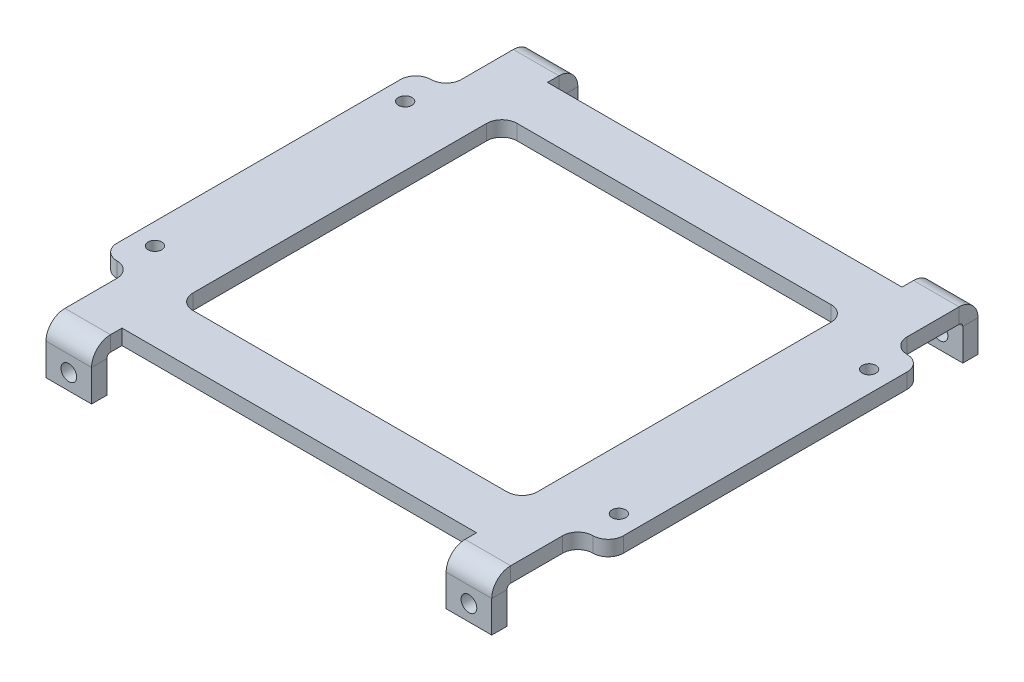
SolidWorks part; units mm, degrees
note: The reader was unsure of these and kept them because the rebuilt part matched: thickness of "Base-Flange1", "Edge-Flange1", "Sheet-Metal1", "Sheet-Metal2", "Sheet-Metal3", "Sheet-Metal4"; flange length of "Edge-Flange1".
material "6061-T6 (SS)"
ref_plane "Front Plane" through (0, 0, 0) normal (0, 0, 1) x (1, 0, 0)
ref_plane "Top Plane" through (0, 0, 0) normal (0, 1, 0) x (1, 0, 0)
ref_plane "Right Plane" through (0, 0, 0) normal (1, 0, 0) x (0, 0, -1)
sketch "Sketch1" plane through (0, 0, 0) normal (0, 1, 0) x (1, 0, 0)
  line L0 (50, -50) -> (-50, -50) construction
  line L1 (50, -50) -> (50, 50) construction
  line L2 (50, 50) -> (-50, 50) construction
  line L3 (-50, -50) -> (-50, 50) construction
  line L4 (50, -50) -> (-50, 50) construction
  line L5 (50, 50) -> (-50, -50) construction
  line L6 (-50, 50) -> (-44, 50) construction
  line L7 (-50, 50) -> (-50, 44) construction
  line L8 (-50, 44) -> (-44, 44) construction
  line L9 (-44, 50) -> (-44, 44) construction
  line L10 (-50, -50) -> (-44, -50) construction
  line L11 (-50, -50) -> (-50, -44) construction
  line L12 (-50, -44) -> (-44, -44) construction
  line L13 (-44, -50) -> (-44, -44) construction
  line L14 (50, -50) -> (44, -50) construction
  line L15 (50, -50) -> (50, -44) construction
  line L16 (50, -44) -> (44, -44) construction
  line L17 (44, -50) -> (44, -44) construction
  line L18 (50, 50) -> (44, 50) construction
  line L19 (50, 50) -> (50, 44) construction
  line L20 (50, 44) -> (44, 44) construction
  line L21 (44, 50) -> (44, 44) construction
  line L22 (-32.625, 45.061) -> (33.923, 45.061) construction
  line L23 (-32.625, 45.061) -> (-32.625, 35.082) construction
  line L24 (-32.625, 35.082) -> (33.923, 35.082) construction
  line L25 (33.923, 45.061) -> (33.923, 35.082) construction
  line L26 (-50, 50) -> (-35, 50)
  line L27 (-50, 50) -> (-50, 48)
  line L28 (-50, 48) -> (-35, 48)
  line L29 (-35, 50) -> (-35, 48)
  line L30 (-50, 50) -> (-48, 50)
  line L31 (-50, 50) -> (-50, 35)
  line L32 (-50, 35) -> (-48, 35)
  line L33 (-48, 50) -> (-48, 35)
  line L34 (50, 50) -> (35, 50)
  line L35 (50, 50) -> (50, 48)
  line L36 (50, 48) -> (35, 48)
  line L37 (35, 50) -> (35, 48)
  line L38 (50, 50) -> (48, 50)
  line L39 (50, 50) -> (50, 35)
  line L40 (50, 35) -> (48, 35)
  line L41 (48, 50) -> (48, 35)
  line L42 (50, -50) -> (48, -50)
  line L43 (50, -50) -> (50, -35)
  line L44 (50, -35) -> (48, -35)
  line L45 (48, -50) -> (48, -35)
  line L46 (50, -50) -> (35, -50)
  line L47 (50, -50) -> (50, -48)
  line L48 (50, -48) -> (35, -48)
  line L49 (35, -50) -> (35, -48)
  line L50 (-50, -50) -> (-35, -50)
  line L51 (-50, -50) -> (-50, -48)
  line L52 (-50, -48) -> (-35, -48)
  line L53 (-35, -50) -> (-35, -48)
  line L54 (-50, -50) -> (-48, -50)
  line L55 (-50, -50) -> (-50, -35)
  line L56 (-50, -35) -> (-48, -35)
  line L57 (-48, -50) -> (-48, -35)
  circle A0 centre (-36.2, 42.85) radius 1.6
  circle A1 centre (37.5, 42.85) radius 1.6
  circle A2 centre (40, -42.85) radius 1.6
  circle A3 centre (-40, -42.85) radius 1.6
  point P0 (0, 0)
  point P5 (0, 0)
  point P6 (0, 0)
  dimension "D6" = 3.2
  dimension "D1" = 100
  dimension "D2" = 6
  dimension "D3" = 6
  dimension "D4" = 6
  dimension "D5" = 6
  dimension "D7" = 7.15
  dimension "D8" = 13.8
  dimension "D9" = 10
  dimension "D10" = 7.15
  dimension "D11" = 10
  dimension "D12" = 7.15
  dimension "D13" = 17.375
  dimension "D14" = 4.939
  dimension "D15" = 14.918
  dimension "D16" = 16.077
  dimension "D17" = 73.7
  dimension "D18" = 15
  dimension "D19" = 2
  dimension "D20" = 15
  dimension "D21" = 2
  dimension "D22" = 2
  dimension "D23" = 15
  dimension "D24" = 15
  dimension "D25" = 2
  dimension "D26" = 15
  dimension "D27" = 2
  dimension "D28" = 2
  dimension "D29" = 15
  dimension "D30" = 15
  dimension "D31" = 15
  dimension "D32" = 2
  dimension "D33" = 2
  dimension "D34" = 100
sketch "Sketch2" plane through (0, 0, 0) normal (0, 1, 0) x (1, 0, 0)
  line L5 (-50, -50) -> (-50, 50) construction
  line L6 (50, -31) -> (-50, -31)
  line L13 (50, -31) -> (50, 31)
  line L14 (50, 31) -> (-50, 31)
  line L16 (-50, -31) -> (-50, 31)
  line L17 (50, -31) -> (-50, 31) construction
  line L18 (50, 31) -> (-50, -31) construction
  line L19 (-50, 48) -> (-35, 48) construction
  line L20 (44, -48) -> (-44, -48)
  line L21 (44, -48) -> (44, 48)
  line L22 (44, 48) -> (-44, 48)
  line L23 (-44, -48) -> (-44, 48)
  line L24 (44, -48) -> (-44, 48) construction
  line L25 (44, 48) -> (-44, -48) construction
  line L26 (-44, 50) -> (-44, 44) construction
  point P0 (0, 0)
  point P8 (0, 0)
  dimension "D1" = 62
sketch "Sketch3" plane through (0, 0, 0) normal (0, 1, 0) x (1, 0, 0)
  line L0 (50, 31) -> (-50, 31) construction
  line L1 (-50, -31) -> (-50, 31) construction
  line L2 (50, -31) -> (-50, -31) construction
  line L3 (50, -31) -> (50, 31) construction
  line L4 (44, 48) -> (-44, 48) construction
  line L5 (-44, -48) -> (-44, 48) construction
  line L6 (44, -48) -> (-44, -48) construction
  line L7 (44, -48) -> (44, 48) construction
  line L8 (50, 31) -> (44, 31)
  line L9 (-50, -31) -> (-50, 31)
  line L10 (50, -31) -> (44, -31)
  line L11 (50, -31) -> (50, 31)
  line L12 (44, 48) -> (35, 48)
  line L13 (-44, -48) -> (-44, -31)
  line L14 (44, -48) -> (35, -48)
  line L15 (44, -48) -> (44, -31)
  line L16 (-44, 31) -> (-50, 31)
  line L17 (-44, 31) -> (-44, 48)
  line L18 (-44, -31) -> (-50, -31)
  line L19 (44, 31) -> (44, 48)
  line L20 (35, 50) -> (35, 48) construction
  line L22 (-35, 48) -> (-35, 42)
  line L23 (-35, 42) -> (35, 42)
  line L24 (35, 48) -> (35, 42)
  line L26 (-35, -48) -> (-35, -42)
  line L27 (-35, -42) -> (35, -42)
  line L28 (35, -48) -> (35, -42)
  line L29 (-35, 48) -> (-44, 48)
  line L30 (34, -32) -> (-34, -32)
  line L31 (34, -32) -> (34, 32)
  line L32 (34, 32) -> (-34, 32)
  line L33 (-34, -32) -> (-34, 32)
  line L34 (34, -32) -> (-34, 32) construction
  line L35 (34, 32) -> (-34, -32) construction
  line L36 (-35, -48) -> (-44, -48)
  point P24 (0, 0)
  dimension "D1" = 6
  dimension "D2" = 10
  dimension "D3" = 10
sketch "Sketch21" plane through (0, 0, 0) normal (0, 1, 0) x (1, 0, 0)
  line L1 (45.8, -24.7) -> (-45.8, -24.7)
  line L2 (45.8, -24.7) -> (45.8, 24.7)
  line L3 (45.8, 24.7) -> (-45.8, 24.7)
  line L4 (-45.8, -24.7) -> (-45.8, 24.7)
  line L5 (45.8, -24.7) -> (-45.8, 24.7) construction
  line L6 (45.8, 24.7) -> (-45.8, -24.7) construction
  point P0 (0, 0)
  dimension "D1" = 91.6
  dimension "D2" = 49.4
base flange "Base-Flange1" sketch "Sketch3" thickness 3 reverse thickness direction no parameters "D1"=0.7366
edge flange "Edge-Flange1" sketch "Sketch16" flange profiles "Sketch16", "Sketch17", "Sketch18", "Sketch19" flange angle 90 flange length 10 flange position material inside bend radius 0.7366 thickness 3 relief rectangular parameters "D6"=10, "D8"=1
sketch "Sketch16" plane through (0, -3, 48) normal (0, 0, -1) x (1, 0, 0)
  line L2 (-44, 0) -> (-44, 7)
  line L3 (-44, 7) -> (-35, 7)
  line L4 (-35, 7) -> (-35, 0)
  line L5 (-35, 0) -> (-44, 0) construction
  line L6 (-35, 0) -> (-44, 0)
sketch "Sketch17" plane through (0, -3, 48) normal (0, 0, -1) x (1, 0, 0)
  line L0 (44, 0) -> (35, 0) construction
  line L1 (44, 0) -> (35, 0)
  line L2 (44, 0) -> (44, 7)
  line L3 (44, 7) -> (35, 7)
  line L4 (35, 7) -> (35, 0)
sketch "Sketch18" plane through (0, -3, -48) normal (0, 0, 1) x (-1, 0, 0)
  line L0 (-35, 0) -> (-44, 0) construction
  line L1 (-35, 0) -> (-44, 0)
  line L2 (-35, 0) -> (-35, 7)
  line L3 (-35, 7) -> (-44, 7)
  line L4 (-44, 7) -> (-44, 0)
sketch "Sketch19" plane through (0, -3, -48) normal (0, 0, 1) x (-1, 0, 0)
  line L0 (44, 0) -> (35, 0) construction
  line L1 (44, 0) -> (35, 0)
  line L2 (44, 0) -> (44, 7)
  line L3 (44, 7) -> (35, 7)
  line L4 (35, 7) -> (35, 0)
bend "EdgeBend1" bend radius 0.7366 bend angle 90 parameters "D5"=1
bend "EdgeBend2" bend radius 0.7366 bend angle 90 parameters "D5"=2
bend "EdgeBend3" bend radius 0.7366 bend angle 90 parameters "D5"=3
bend "EdgeBend4" bend radius 0.7366 bend angle 90 parameters "D5"=4
fillet "Fillet1" radius 3 8 edges at (44, -1.5, -31) (-44, -1.5, -31) (-44, -1.5, 31) (34, -1.5, -32) (34, -1.5, 32) (-34, -1.5, 32) (-34, -1.5, -32) (44, -1.5, 31)
fillet "Fillet2" radius 3 4 edges at (50, -1.5, -31) (50, -1.5, 31) (-50, -1.5, 31) (-50, -1.5, -31)
sketch "Sketch20" plane through (0, 0, 48) normal (0, 0, 1) x (1, 0, 0)
  line L1 (-44, -10) -> (-44, -3.7366) construction
  line L2 (-35, -10) -> (-44, -10) construction
  line L3 (44, -10) -> (35, -10) construction
  circle A0 centre (-39.5, -6.8683) radius 1.55
  circle A1 centre (39.5, -6.8683) radius 1.55
  point P8 (-44, -6.8683)
  point P9 (-39.5, -10)
  point P12 (39.5, -10)
  dimension "D1" = 3.1
  dimension "D2" = 3.1
extrude "Cut-Extrude1" cut sketch "Sketch20" against normal through all normal cut yes
sketch "Sketch22" plane through (0, 0, 0) normal (0, 1, 0) x (1, 0, 0)
  circle A0 centre (-45.8, 24.7) radius 1.35
  circle A1 centre (-45.8, -24.7) radius 1.35
  circle A2 centre (45.8, 24.7) radius 1.35
  circle A3 centre (45.8, -24.7) radius 1.35
  dimension "D1" = 2.7
extrude "Cut-Extrude2" cut sketch "Sketch22" against normal through all normal cut yes
sketch "Bend-Lines1" [suppressed] plane through (0, 0, 0) normal (0, 1, 0) x (1, 0, 0)
sketch "Bounding-Box1" [suppressed] plane through (0, 0, 0) normal (0, 1, 0) x (1, 0, 0)
sheet metal parameters "Sheet-Metal1" thickness 3 parameters "D1"=0.7366
flat pattern "Flat-Pattern1" [suppressed]
sketch "Bend-Lines2" plane through (0, 0, 0) normal (0, 1, 0) x (1, 0, 0)
sketch3d "Bounding-Box2" [suppressed]
  line L0 (50, -48, 0) -> (-50, -48, 0) construction
  line L1 (50, 48, 0) -> (-50, 48, 0) construction
  line L2 (50, -48, 0) -> (50, 48, 0) construction
  line L3 (-50, -48, 0) -> (-50, 48, 0) construction
sheet metal parameters "Sheet-Metal2" thickness 3 parameters "D1"=0.7366, "D7"=2.5
flat pattern "Flat-Pattern1"
sketch "Bend-Lines2" plane through (0, 0, 0) normal (0, 1, 0) x (1, 0, 0)
  line L0 (-35, 46.02) -> (-44, 46.02) construction
  line L1 (44, 46.02) -> (35, 46.02) construction
  line L2 (35, -46.02) -> (44, -46.02) construction
  line L3 (-44, -46.02) -> (-35, -46.02) construction
  line L4 (-35, 46.02) -> (-44, 46.02) construction
  line L5 (44, 46.02) -> (35, 46.02) construction
  line L6 (35, -46.02) -> (44, -46.02) construction
  line L7 (-44, -46.02) -> (-35, -46.02) construction
sketch3d "Bounding-Box2" [suppressed]
  line L0 (50, 54.6473, 0) -> (50, -54.6473, 0) construction
  line L1 (-50, 54.6473, 0) -> (-50, -54.6473, 0) construction
  line L2 (50, 54.6473, 0) -> (-50, 54.6473, 0) construction
  line L3 (50, -54.6473, 0) -> (-50, -54.6473, 0) construction
bend of the flat pattern "Flatten-<EdgeBend1>1"
bend of the flat pattern "Flatten-<EdgeBend2>1"
bend of the flat pattern "Flatten-<EdgeBend3>1"
bend of the flat pattern "Flatten-<EdgeBend4>1"
sheet metal parameters "Sheet-Metal3" thickness 3 parameters "D1"=0.7366, "D7"=2.5
flat pattern "Flat-Pattern1"
sketch "Bend-Lines2" plane through (0, 0, 0) normal (0, 1, 0) x (1, 0, 0)
  line L0 (-35, 46.02) -> (-44, 46.02) construction
  line L1 (44, 46.02) -> (35, 46.02) construction
  line L2 (35, -46.02) -> (44, -46.02) construction
  line L3 (-44, -46.02) -> (-35, -46.02) construction
  line L4 (-35, 46.02) -> (-44, 46.02) construction
  line L5 (44, 46.02) -> (35, 46.02) construction
  line L6 (35, -46.02) -> (44, -46.02) construction
  line L7 (-44, -46.02) -> (-35, -46.02) construction
sketch3d "Bounding-Box2" [suppressed]
  line L0 (50, 54.6473, 0) -> (50, -54.6473, 0) construction
  line L1 (-50, 54.6473, 0) -> (-50, -54.6473, 0) construction
  line L2 (50, 54.6473, 0) -> (-50, 54.6473, 0) construction
  line L3 (50, -54.6473, 0) -> (-50, -54.6473, 0) construction
bend of the flat pattern "Flatten-<EdgeBend1>1"
bend of the flat pattern "Flatten-<EdgeBend2>1"
bend of the flat pattern "Flatten-<EdgeBend3>1"
bend of the flat pattern "Flatten-<EdgeBend4>1"
sheet metal parameters "Sheet-Metal4" thickness 3 parameters "D1"=0.7366, "D7"=2.5
flat pattern "Flat-Pattern1"
sketch "Bend-Lines2" plane through (0, 0, 0) normal (0, 1, 0) x (1, 0, 0)
  line L0 (-35, 46.02) -> (-44, 46.02) construction
  line L1 (44, 46.02) -> (35, 46.02) construction
  line L2 (35, -46.02) -> (44, -46.02) construction
  line L3 (-44, -46.02) -> (-35, -46.02) construction
  line L4 (-35, 46.02) -> (-44, 46.02) construction
  line L5 (44, 46.02) -> (35, 46.02) construction
  line L6 (35, -46.02) -> (44, -46.02) construction
  line L7 (-44, -46.02) -> (-35, -46.02) construction
sketch3d "Bounding-Box2" [suppressed]
  line L0 (50, 54.04, 0) -> (50, -54.04, 0) construction
  line L1 (-50, 54.04, 0) -> (-50, -54.04, 0) construction
  line L2 (50, 54.04, 0) -> (-50, 54.04, 0) construction
  line L3 (50, -54.04, 0) -> (-50, -54.04, 0) construction
bend of the flat pattern "Flatten-<EdgeBend1>1"
bend of the flat pattern "Flatten-<EdgeBend2>1"
bend of the flat pattern "Flatten-<EdgeBend3>1"
bend of the flat pattern "Flatten-<EdgeBend4>1"
